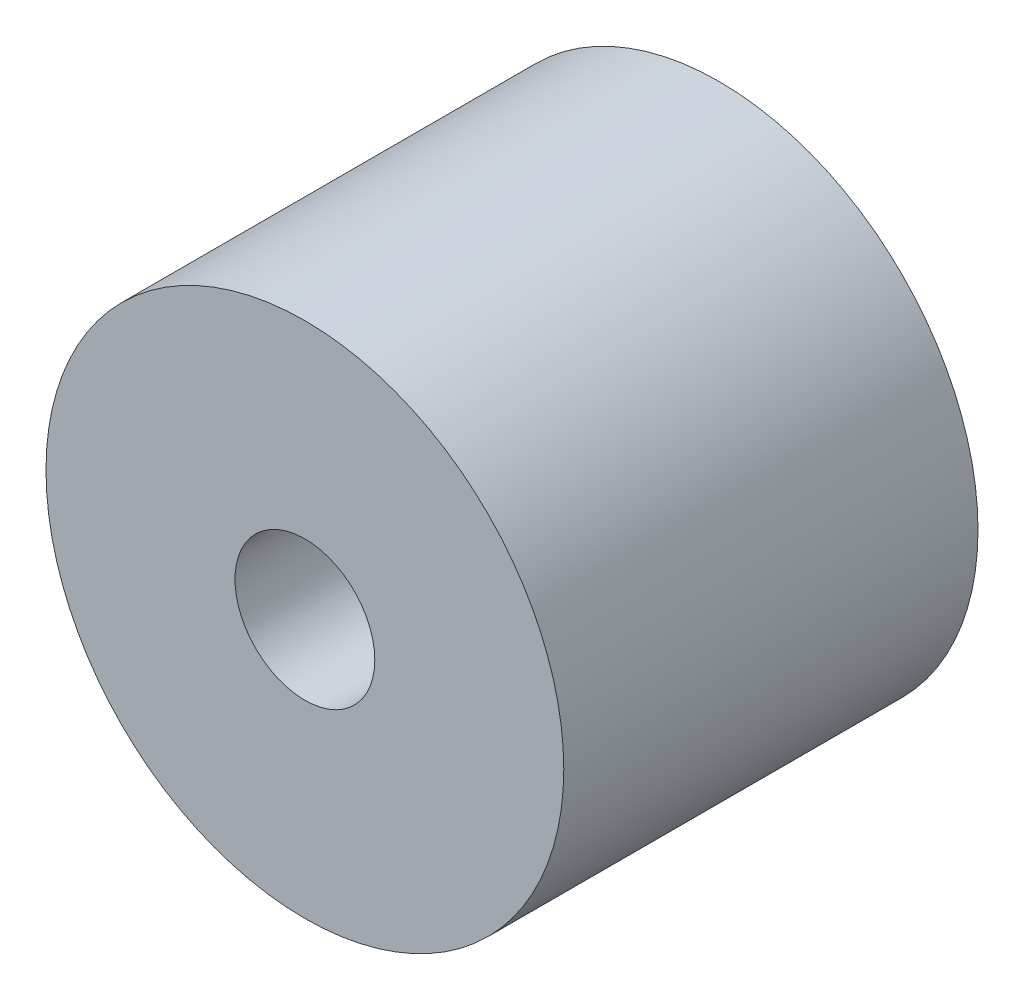
SolidWorks part; units mm, degrees
material "Brass"
ref_plane "Front Plane" through (0, 0, 0) normal (0, 0, 1) x (1, 0, 0)
ref_plane "Top Plane" through (0, 0, 0) normal (0, 1, 0) x (1, 0, 0)
ref_plane "Right Plane" through (0, 0, 0) normal (1, 0, 0) x (0, 0, -1)
ref_axis "X-axis" through (-88.99, 0, 0) along (1, 0, 0)
ref_axis "Y-axis" through (0, 55, 0) along (0, -1, 0)
ref_axis "Z-axis" through (0, 0, -88.99) along (0, 0, 1)
sketch "Sketch1" plane through (0, 0, 0) normal (0, 0, 1) x (1, 0, 0)
  circle A0 centre (0, 0) radius 6.35
  dimension "D1" = 12.7
extrude "Boss-Extrude1" add sketch "Sketch1" against normal blind 10.16
hole_wizard "1/4 (0.135) Diameter Hole1" positions "Sketch2" profile "Sketch3" hole size "1/4" standard "ANSI Inch" end condition through all
sketch "Sketch2" plane through (0, 0, 0) normal (0, 0, 1) x (1, 0, 0)
  point P0 (0, 0)
sketch "Sketch3" plane through (0, 0, 0) normal (1, 0, 0) x (0, -1, 0)
  line L0 (0, 0) -> (0, 10.16)
  line L1 (0, 10.16) -> (1.7145, 10.16)
  line L2 (1.7145, 10.16) -> (1.7145, 0)
  line L5 (1.7145, 0) -> (0, 0)
  line L11 (0, -6.35) -> (0, 107.95) construction
  dimension "Thru Hole Dia." = 3.429
  dimension "Thru Hole Depth" = 10.16
